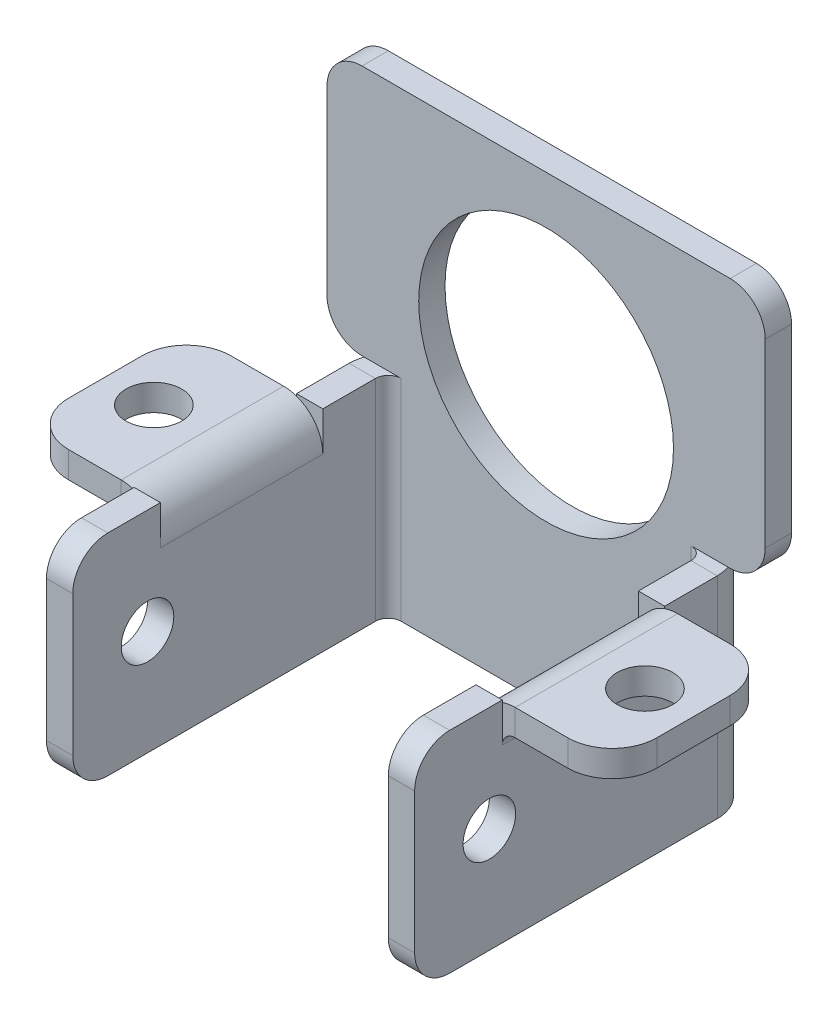
SolidWorks part; units mm, degrees
note: The reader was unsure of these and kept them because the rebuilt part matched: flange length of "Edge-Flange1", "Edge-Flange3".
material "Wrought Stainless Steel"
ref_plane "Front Plane" through (0, 0, 0) normal (0, 0, 1) x (1, 0, 0)
ref_plane "Top Plane" through (0, 0, 0) normal (0, 1, 0) x (1, 0, 0)
ref_plane "Right Plane" through (0, 0, 0) normal (1, 0, 0) x (0, 0, -1)
sketch "Sketch1" plane through (0, 0, 0) normal (0, 0, 1) x (1, 0, 0)
  line L8 (-9, -16.3187) -> (9, -16.3187) construction
  line L9 (-9, -16.3187) -> (9, -16.3187)
  line L10 (-12.5, -4.3188) -> (-9, -4.3188)
  line L11 (12.5, -4.3188) -> (9, -4.3188)
  line L14 (-8.7313, -10.3188) -> (8.7312, -10.3188) construction
  line L16 (-9, -12) -> (-9, -15.3187)
  line L17 (-9, -15.3187) -> (9, -15.3187)
  line L18 (9, -15.3187) -> (9, -12)
  line L19 (11, -10) -> (12.5, -10)
  line L20 (12.5, -10) -> (12.5, 10)
  line L21 (12.5, 10) -> (-12.5, 10)
  line L22 (-12.5, 10) -> (-12.5, -10)
  line L23 (-12.5, -10) -> (-11, -10)
  line L24 (-9, -4.3188) -> (-9, -16.3187)
  line L26 (9, -16.3187) -> (9, -4.3188)
  line L28 (12.5, -4.3188) -> (12.5, 10)
  line L29 (12.5, 10) -> (-12.5, 10)
  line L30 (-12.5, 10) -> (-12.5, -4.3188)
  circle A4 centre (0, 0) radius 7.2667 construction
  circle A5 centre (0, 0) radius 7.2667
  arc A8 (11, -10) -> (9, -12) centre (11, -12) ccw
  arc A9 (-9, -12) -> (-11, -10) centre (-11, -12) ccw
  dimension "D1" = 1
  dimension "D2" = 6
sheet metal parameters "Sheet-Metal1" thickness 1.5 parameters "D1"=0.7366
base flange "Base-Flange1" sketch "Sketch1" thickness 1.5 reverse thickness direction yes parameters "D1"=0.7366
edge flange "Edge-Flange1" sketch "Sketch7" flange profiles "Sketch7", "Sketch8" flange angle 90 flange length 18 bend radius 0.7366 thickness 1.5 parameters "D6"=10, "D8"=0.254
sketch "Sketch7" plane through (-9, 0, 1.5) normal (-1, 0, 0) x (0, -1, 0)
  line L0 (4.3188, 0) -> (16.3187, 0) construction
  line L1 (4.3188, 0) -> (16.3187, 0)
  line L2 (4.3188, 0) -> (4.3188, 18)
  line L3 (4.3188, 18) -> (16.3187, 18)
  line L4 (16.3187, 18) -> (16.3187, 0)
sketch "Sketch8" plane through (9, 0, 1.5) normal (1, 0, 0) x (0, 1, 0)
  line L0 (-16.3187, 0) -> (-4.3188, 0) construction
  line L1 (-16.3187, 0) -> (-4.3188, 0)
  line L2 (-16.3187, 0) -> (-16.3187, 18)
  line L3 (-16.3187, 18) -> (-4.3188, 18)
  line L4 (-4.3188, 18) -> (-4.3188, 0)
bend "EdgeBend1" bend radius 0.7366 bend angle 90 parameters "D5"=1
bend "EdgeBend2" bend radius 0.7366 bend angle 90 parameters "D5"=2
sketch "Sketch9" plane through (10.5, 0, 0) normal (1, 0, 0) x (0, 0, -1)
  line L0 (-2.2366, -4.3188) -> (-2.2366, -16.3187) construction
  line L1 (-19.5, -16.3187) -> (-2.2366, -16.3187) construction
  circle A0 centre (-15.2366, -10.3187) radius 1.5
  dimension "D1" = 13
  dimension "D2" = 6
  dimension "D3" = 3
extrude "Cut-Extrude1" cut sketch "Sketch9" against normal through all
fillet "Fillet1" radius 2 8 edges at (-12.5, -4.3188, 0.75) (-9.75, -16.3187, 19.5) (-9.75, -4.3188, 19.5) (9.75, -16.3187, 19.5) (9.75, -4.3188, 19.5) (12.5, -4.3188, 0.75) (12.5, 10, 0.75) (-12.5, 10, 0.75)
edge flange "Edge-Flange3" sketch "Sketch19" flange angle 90 flange length 6.2766 flange position material inside bend radius 0.7366 thickness 1.5 parameters "D6"=10
sketch "Sketch19" plane through (10.5, -4.3188, 0) normal (0, 1, 0) x (0, 0, 1)
  line L0 (2.2366, 0) -> (17.5, 0) construction
  line L1 (5.2366, 0) -> (14.5, 0)
  line L2 (5.2366, 0) -> (5.2366, 6.2766)
  line L3 (5.2366, 6.2766) -> (14.5, 6.2766)
  line L4 (14.5, 6.2766) -> (14.5, 0)
  dimension "D1" = 3
  dimension "D2" = 3
bend "EdgeBend5" bend radius 0.7366 bend angle 90 parameters "D5"=3
fillet "Fillet2" radius 2.54 2 edges at (16.7766, -5.0688, 5.2366) (16.7766, -5.0688, 14.5)
mirror "Mirror1" about plane through (0, 0, 0) normal (1, 0, 0) of "Fillet2", "Edge-Flange3"
bend "MirrorBend1" bend radius 0.7366 bend angle 90 parameters "D5"=4
sketch "Sketch20" plane through (0, -4.3188, 0) normal (0, 1, 0) x (1, 0, 0)
  line L0 (-11.2366, -9.8683) -> (-16.7766, -9.8683) construction
  line L1 (-11.2366, -5.2366) -> (-11.2366, -14.5) construction
  line L2 (-16.7766, -11.96) -> (-16.7766, -7.7766) construction
  line L3 (11.2366, -9.8683) -> (16.7766, -9.8683) construction
  line L4 (11.2366, -14.5) -> (11.2366, -5.2366) construction
  line L5 (16.7766, -11.96) -> (16.7766, -7.7766) construction
  circle A0 centre (14.0066, -9.8683) radius 1.5875
  circle A1 centre (-14.0066, -9.8683) radius 1.5875
  dimension "D1" = 3.175
extrude "Cut-Extrude3" cut sketch "Sketch20" against normal blind 2.54
ref_plane "Center Plane" through (0, -10.3187, 0) normal (0, 1, 0) x (-1, 0, 0)
flat pattern "Flat-Pattern1" [suppressed]
sketch "Bend-Lines1" plane through (0, 0, 1.5) normal (0, 0, 1) x (1, 0, 0)
  line L0 (-13.5985, -5.3878) -> (-22.8619, -5.3878) construction
  line L1 (13.5985, -5.3878) -> (22.8619, -5.3878) construction
  line L2 (9.431, -4.3187) -> (9.431, -16.3187) construction
  line L3 (-9.431, -16.3187) -> (-9.431, -4.3187) construction
  line L4 (-13.5985, -5.3878) -> (-22.8619, -5.3878) construction
  line L5 (13.5985, -5.3878) -> (22.8619, -5.3878) construction
  line L6 (9.431, -4.3187) -> (9.431, -16.3187) construction
  line L7 (-9.431, -16.3187) -> (-9.431, -4.3187) construction
bend of the flat pattern "Flatten-<EdgeBend1>1"
bend of the flat pattern "Flatten-<EdgeBend2>1"
bend of the flat pattern "Flatten-<EdgeBend5>1"
bend of the flat pattern "Flatten-<MirrorBend1>1"
